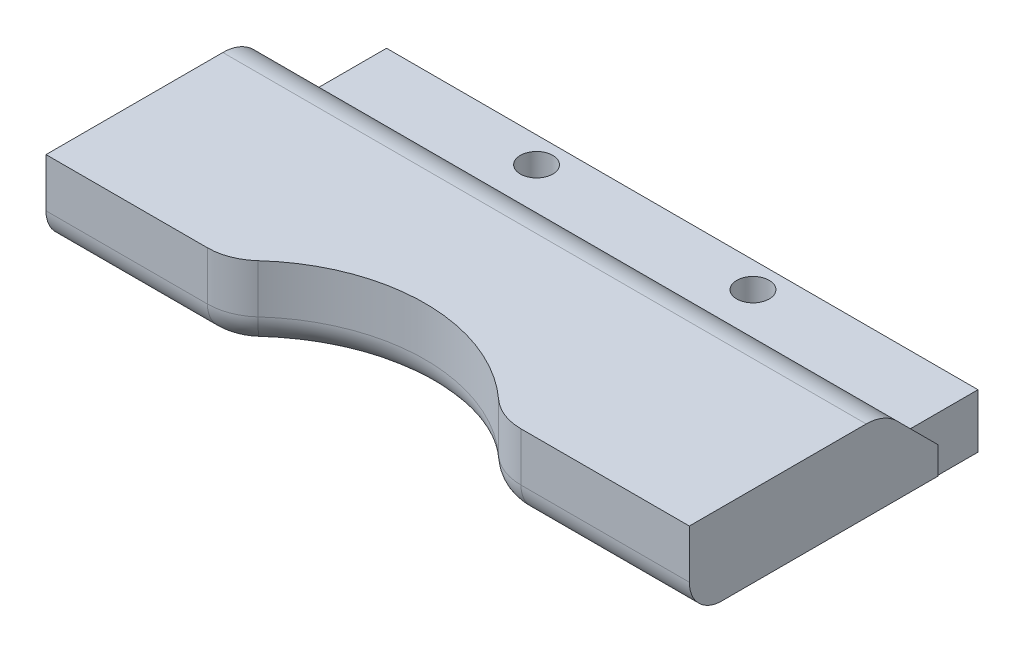
SolidWorks part; units mm, degrees
ref_plane "Front Plane" through (0, 0, 0) normal (0, 0, 1) x (1, 0, 0)
ref_plane "Top Plane" through (0, 0, 0) normal (0, 1, 0) x (1, 0, 0)
ref_plane "Right Plane" through (0, 0, 0) normal (1, 0, 0) x (0, 0, -1)
sketch "草图1" plane through (0, 0, 0) normal (0, 1, 0) x (1, 0, 0)
  line L0 (0, 0) -> (0, -9.0163) construction
  line L1 (0, 0) -> (-22.0911, 0) construction
  line L3 (-26.2566, -6.11) -> (28.4077, -6.11)
  line L4 (-26.2566, -6.11) -> (-26.2566, -11.11)
  line L5 (-26.2566, -11.11) -> (28.4077, -11.11)
  line L6 (28.4077, -6.11) -> (28.4077, -11.11)
  circle A0 centre (-10, -8.5) radius 1.5
  circle A1 centre (10, -8.5) radius 1.5
  dimension "D1" = 3
  dimension "D2" = 8.5
  dimension "D3" = 10
  dimension "D4" = 2.61
  dimension "D5" = 5
extrude "凸台-拉伸1" add sketch "草图1" along normal blind 5 contours L4 L3 L6 L5 | A0 | A1
sketch "草图2" plane through (0, 0, 11.11) normal (0, 0, 1) x (1, 0, 0)
  line L0 (0, 0) -> (0, 5) construction
  line L1 (-26.2566, 5) -> (28.4077, 5) construction
  line L3 (-29.7301, 3.7502) -> (29.7301, 3.7502)
  line L4 (-29.7301, 3.7502) -> (-29.7301, 1.2498)
  line L5 (-29.7301, 1.2498) -> (29.7301, 1.2498)
  line L6 (29.7301, 3.7502) -> (29.7301, 1.2498)
  line L7 (-29.7301, 3.7502) -> (29.7301, 1.2498) construction
  line L8 (-29.7301, 1.2498) -> (29.7301, 3.7502) construction
  point P5 (0, 2.5)
extrude "凸台-拉伸2" add sketch "草图2" along normal blind 23
fillet "圆角1" [suppressed] radius 2
sketch "草图5" plane through (0, 3.7502, 0) normal (0, 1, 0) x (1, 0, 0)
  circle A0 centre (-0.32, -44.9941) radius 16.5
  dimension "D1" = 33
extrude "切除-拉伸1" cut sketch "草图5" against normal blind 15
fillet "圆角2" [suppressed] radius 3
sketch "草图6" plane through (0, 3.7502, 0) normal (0, 1, 0) x (1, 0, 0)
  line L4 (29.7301, -11.11) -> (28.4077, -11.11)
  line L6 (-29.7301, -11.11) -> (-29.7301, -34.11)
  line L7 (-29.7301, -11.11) -> (-29.7301, -34.11)
  line L8 (-29.7301, -34.11) -> (-12.721, -34.11)
  line L9 (-29.7301, -34.11) -> (-12.721, -34.11)
  line L10 (29.7301, -34.11) -> (29.7301, -11.11)
  line L22 (29.7301, -34.11) -> (29.7301, -11.11)
  line L23 (29.7301, -11.11) -> (28.4077, -11.11)
  line L25 (28.4077, -11.11) -> (-26.2566, -11.11)
  line L26 (28.4077, -11.11) -> (-26.2566, -11.11)
  line L27 (12.081, -34.11) -> (29.7301, -34.11)
  line L29 (12.081, -34.11) -> (29.7301, -34.11)
  line L30 (-26.2566, -11.11) -> (-29.7301, -11.11)
  line L31 (-26.2566, -11.11) -> (-29.7301, -11.11)
  arc A1 (12.081, -34.11) -> (-12.721, -34.11) centre (-0.32, -44.9941) ccw
  arc A2 (12.081, -34.11) -> (-12.721, -34.11) centre (-0.32, -44.9941) ccw
  dimension "D1" = 0
fillet "圆角3" [suppressed] radius 3
sketch "草图7" plane through (0, 3.7502, 0) normal (0, 1, 0) x (1, 0, 0)
  line L6 (-29.7301, -34.11) -> (-12.721, -34.11)
  line L9 (29.7301, -34.11) -> (29.7301, -11.11)
  line L10 (29.7301, -11.11) -> (28.4077, -11.11)
  line L11 (28.4077, -11.11) -> (-26.2566, -11.11)
  line L12 (29.7301, -11.11) -> (28.4077, -11.11)
  line L13 (-29.7301, -11.11) -> (-29.7301, -34.11)
  line L16 (29.7301, -34.11) -> (29.7301, -11.11)
  line L18 (28.4077, -11.11) -> (-26.2566, -11.11)
  line L20 (-29.7301, -11.11) -> (-29.7301, -34.11)
  line L22 (-29.7301, -34.11) -> (-12.721, -34.11)
  line L24 (-26.2566, -11.11) -> (-29.7301, -11.11)
  line L25 (-26.2566, -11.11) -> (-29.7301, -11.11)
  line L26 (12.081, -34.11) -> (29.7301, -34.11)
  line L27 (12.081, -34.11) -> (29.7301, -34.11)
  arc A1 (12.081, -34.11) -> (-12.721, -34.11) centre (-0.32, -44.9941) ccw
  arc A2 (12.081, -34.11) -> (-12.721, -34.11) centre (-0.32, -44.9941) ccw
  dimension "D1" = 0
extrude "凸台-拉伸3" add sketch "草图7" along normal blind 5
fillet "圆角4" [suppressed] radius 4
chamfer "倒角1" distance 5 angle 45 1 edges at (0, 8.7502, 11.11)
fillet "圆角5" [suppressed] radius 10
fillet "圆角6" radius 10 1 edges at (1.0755, 1.2498, 11.11)
fillet "圆角7" radius 4 1 edges at (0, 8.7502, 16.11)
sketch "草图8" plane through (0, 8.7502, 0) normal (0, 1, 0) x (1, 0, 0)
  line L0 (29.7301, -17.7669) -> (-29.7301, -17.7669) construction
  line L1 (8.2841, -17.7669) -> (-8.9957, -17.7669)
  line L2 (8.2841, -17.7669) -> (8.2841, -19.7741)
  line L3 (8.2841, -19.7741) -> (-8.9957, -19.7741)
  line L4 (-8.9957, -17.7669) -> (-8.9957, -19.7741)
extrude "凸台-拉伸5" [suppressed] add sketch "草图8" along normal blind 10
fillet "圆角8" radius 5 2 edges at (-12.721, 5, 34.11) (12.081, 5, 34.11)
sketch "草图9" plane through (-29.7301, 0, 0) normal (-1, 0, 0) x (0, 0, 1)
  line L5 (34.11, 6.2498) -> (29.11, 1.2498)
  line L6 (34.11, 1.2498) -> (11.11, 1.2498) construction
  line L7 (29.11, 1.2498) -> (34.11, 1.2498)
  line L8 (34.11, 1.2498) -> (34.11, 6.2498)
  point P4 (0, 0)
  dimension "D1" = 45
  dimension "D2" = 5
sketch "草图12" plane through (0, 8.7502, 0) normal (0, 1, 0) x (1, 0, 0)
  line L0 (14.1695, -34.11) -> (29.7301, -34.11) construction
  line L1 (-29.7301, -34.11) -> (-14.8095, -34.11) construction
  line L2 (14.1695, -34.11) -> (29.7301, -34.11)
  line L3 (-29.7301, -34.11) -> (-14.8095, -34.11)
  arc A0 (10.7998, -32.804) -> (14.1695, -34.11) centre (14.1695, -29.11) ccw construction
  arc A1 (10.7998, -32.804) -> (-11.4398, -32.804) centre (-0.32, -44.9941) ccw construction
  arc A2 (-14.8095, -34.11) -> (-11.4398, -32.804) centre (-14.8095, -29.11) ccw construction
  arc A3 (10.7998, -32.804) -> (14.1695, -34.11) centre (14.1695, -29.11) ccw
  arc A4 (10.7998, -32.804) -> (-11.4398, -32.804) centre (-0.32, -44.9941) ccw
  arc A5 (-14.8095, -34.11) -> (-11.4398, -32.804) centre (-14.8095, -29.11) ccw
sweep "切除-扫描1" [suppressed] cut profiles "草图9" path "草图12"
fillet "圆角9" radius 3 5 edges at (21.9498, 1.2498, 34.11) (12.3625, 1.2498, 33.7721) (-22.2698, 1.2498, 34.11) (-13.0025, 1.2498, 33.7721) (-0.32, 1.2498, 28.4941)
